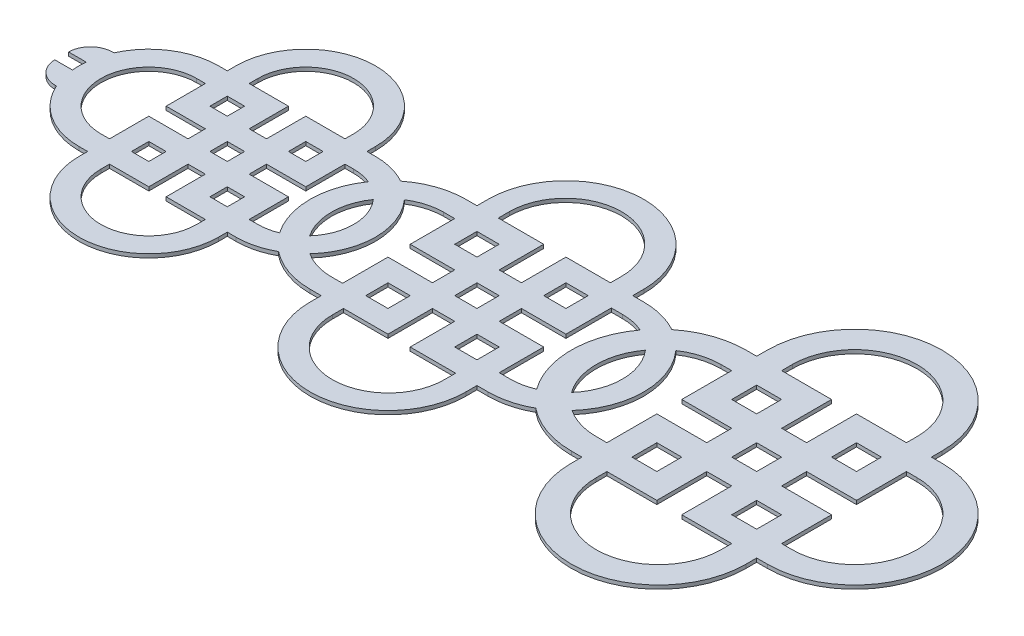
SolidWorks part; units mm, degrees
material "Acrylic (Medium-high impact)"
ref_plane "Front Plane" through (0, 0, 0) normal (0, 0, 1) x (1, 0, 0)
ref_plane "Top Plane" through (0, 0, 0) normal (0, 1, 0) x (1, 0, 0)
ref_plane "Right Plane" through (0, 0, 0) normal (1, 0, 0) x (0, 0, -1)
sketch "스케치1" plane through (0, 0, 0) normal (0, 1, 0) x (1, 0, 0)
  line L0 (0, 10.16) -> (0, -10.16) construction
  line L1 (-50.8, -10.16) -> (50.8, -10.16) construction
  line L2 (-50.8, -10.16) -> (-50.8, 10.16) construction
  line L3 (-50.8, 10.16) -> (50.8, 10.16) construction
  line L4 (50.8, -10.16) -> (50.8, 10.16) construction
  line L5 (-50.8, -10.16) -> (50.8, 10.16) construction
  line L6 (-50.8, 10.16) -> (50.8, -10.16) construction
  line L7 (-35.2629, 0) -> (-46.0171, 0) construction
  line L8 (-45.4229, -4.7829) -> (-35.8571, -4.7829)
  line L9 (-45.4229, -4.7829) -> (-45.4229, 4.7829)
  line L10 (-45.4229, 4.7829) -> (-35.8571, 4.7829)
  line L11 (-35.8571, -4.7829) -> (-35.8571, 4.7829)
  line L12 (-45.4229, -4.7829) -> (-35.8571, 4.7829) construction
  line L13 (-45.4229, 4.7829) -> (-35.8571, -4.7829) construction
  line L14 (-45.4229, 10.16) -> (-35.8571, 10.16)
  line L15 (-45.4229, 10.16) -> (-45.4229, 0.5943)
  line L16 (-45.4229, 0.5943) -> (-35.8571, 0.5943)
  line L17 (-35.8571, 10.16) -> (-35.8571, 0.5943)
  line L18 (-45.4229, 10.16) -> (-35.8571, 0.5943) construction
  line L19 (-45.4229, 0.5943) -> (-35.8571, 10.16) construction
  line L20 (-45.4229, -10.16) -> (-35.8571, -10.16)
  line L21 (-45.4229, -10.16) -> (-45.4229, -0.5943)
  line L22 (-45.4229, -0.5943) -> (-35.8571, -0.5943)
  line L23 (-35.8571, -10.16) -> (-35.8571, -0.5943)
  line L24 (-45.4229, -10.16) -> (-35.8571, -0.5943) construction
  line L25 (-45.4229, -0.5943) -> (-35.8571, -10.16) construction
  line L26 (-30.48, -4.7829) -> (-40.0457, -4.7829)
  line L27 (-30.48, -4.7829) -> (-30.48, 4.7829)
  line L28 (-30.48, 4.7829) -> (-40.0457, 4.7829)
  line L29 (-40.0457, -4.7829) -> (-40.0457, 4.7829)
  line L30 (-30.48, -4.7829) -> (-40.0457, 4.7829) construction
  line L31 (-30.48, 4.7829) -> (-40.0457, -4.7829) construction
  line L32 (-50.8, -4.7829) -> (-41.2343, -4.7829)
  line L33 (-50.8, -4.7829) -> (-50.8, 4.7829)
  line L34 (-50.8, 4.7829) -> (-41.2343, 4.7829)
  line L35 (-41.2343, -4.7829) -> (-41.2343, 4.7829)
  line L36 (-50.8, -4.7829) -> (-41.2343, 4.7829) construction
  line L37 (-50.8, 4.7829) -> (-41.2343, -4.7829) construction
  line L38 (-40.64, 5.3771) -> (-40.64, -5.3771) construction
  line L39 (-49.3, -3.2829) -> (-49.3, 3.2829)
  line L40 (-49.3, 3.2829) -> (-42.7343, 3.2829)
  line L41 (-42.7343, -3.2829) -> (-42.7343, 3.2829)
  line L42 (-49.3, -3.2829) -> (-42.7343, -3.2829)
  line L43 (-43.9229, 8.66) -> (-43.9229, 2.0943)
  line L44 (-43.9229, 2.0943) -> (-37.3571, 2.0943)
  line L45 (-37.3571, 8.66) -> (-37.3571, 2.0943)
  line L46 (-43.9229, 8.66) -> (-37.3571, 8.66)
  line L47 (-40.0457, 0) -> (-41.2343, 0) construction
  line L48 (-38.5457, -3.2829) -> (-31.98, -3.2829)
  line L49 (-38.5457, -3.2829) -> (-38.5457, 3.2829)
  line L50 (-38.5457, 3.2829) -> (-31.98, 3.2829)
  line L51 (-31.98, -3.2829) -> (-31.98, 3.2829)
  line L52 (-38.5457, -3.2829) -> (-31.98, 3.2829) construction
  line L53 (-38.5457, 3.2829) -> (-31.98, -3.2829) construction
  line L58 (-43.9229, 3.1779) -> (-42.7343, 3.1779) construction
  line L60 (-43.9229, -2.0943) -> (-37.3571, -2.0943)
  line L61 (-43.9229, -2.0943) -> (-43.9229, -8.66)
  line L62 (-43.9229, -8.66) -> (-37.3571, -8.66)
  line L63 (-37.3571, -2.0943) -> (-37.3571, -8.66)
  line L64 (-43.9229, -2.0943) -> (-37.3571, -8.66) construction
  line L65 (-43.9229, -8.66) -> (-37.3571, -2.0943) construction
  point P0 (0, 0)
  point P8 (-40.64, 0)
  point P13 (-40.64, 5.3771)
  point P18 (-40.64, -5.3771)
  point P23 (-35.2629, 0)
  point P28 (-46.0171, 0)
  point P39 (-43.7716, 3.1316)
  dimension "D1" = 20.32
  dimension "D2" = 101.6
  dimension "D3" = 1.5
  dimension "D4" = 1.5
  dimension "D5" = 1.5
  dimension "D6" = 1.5
  dimension "D7" = 1.5
  dimension "D8" = 1.5
  dimension "D9" = 1.5
  dimension "D10" = 1.5
  dimension "D11" = 1.5
sketch "스케치2" plane through (0, 0, 0) normal (0, 1, 0) x (1, 0, 0)
  line L0 (-50.8, 4.7829) -> (-41.2343, 4.7829) construction
  line L1 (-50.8, -4.7829) -> (-41.2343, -4.7829) construction
  line L2 (-46.0171, 4.7829) -> (-45.4229, 4.7829)
  line L3 (-35.8571, 5.3771) -> (-35.8571, 4.7829)
  line L5 (-46.0171, -4.7829) -> (-45.4229, -4.7829)
  line L6 (-37.3571, 5.3771) -> (-37.3571, 4.7829)
  line L8 (-43.9229, 4.7829) -> (-43.9229, 5.3771)
  line L10 (-45.4229, 5.3771) -> (-45.4229, 4.7829)
  line L12 (-35.2629, -4.7829) -> (-35.8571, -4.7829)
  line L14 (-35.2629, -3.2829) -> (-35.8571, -3.2829)
  line L16 (-43.9229, 2.0943) -> (-43.9229, 3.2829)
  line L17 (-49.3, 3.2829) -> (-42.7343, 3.2829) construction
  line L18 (-43.9229, 8.66) -> (-43.9229, 2.0943) construction
  line L19 (-43.9229, 3.2829) -> (-42.7343, 3.2829)
  line L20 (-42.7343, 3.2829) -> (-42.7343, 2.0943)
  line L21 (-42.7343, -3.2829) -> (-42.7343, 3.2829) construction
  line L22 (-43.9229, 2.0943) -> (-37.3571, 2.0943) construction
  line L23 (-42.7343, 2.0943) -> (-43.9229, 2.0943)
  line L24 (-41.2343, 0.5943) -> (-41.2343, -0.5943)
  line L25 (-45.4229, 0.5943) -> (-35.8571, 0.5943) construction
  line L26 (-41.2343, -4.7829) -> (-41.2343, 4.7829) construction
  line L27 (-45.4229, -0.5943) -> (-35.8571, -0.5943) construction
  line L28 (-41.2343, -0.5943) -> (-40.0457, -0.5943)
  line L29 (-40.0457, -0.5943) -> (-40.0457, 0.5943)
  line L30 (-40.0457, -4.7829) -> (-40.0457, 4.7829) construction
  line L31 (-40.0457, 0.5943) -> (-41.2343, 0.5943)
  line L32 (-43.9229, -2.0943) -> (-42.7343, -2.0943)
  line L33 (-43.9229, -2.0943) -> (-37.3571, -2.0943) construction
  line L34 (-42.7343, -2.0943) -> (-42.7343, -3.2829)
  line L35 (-42.7343, -3.2829) -> (-43.9229, -3.2829)
  line L36 (-49.3, -3.2829) -> (-42.7343, -3.2829) construction
  line L37 (-43.9229, -3.2829) -> (-43.9229, -2.0943)
  line L38 (-37.3571, -2.0943) -> (-37.3571, -3.2829)
  line L39 (-38.5457, -3.2829) -> (-31.98, -3.2829) construction
  line L40 (-37.3571, -2.0943) -> (-37.3571, -8.66) construction
  line L41 (-37.3571, -3.2829) -> (-38.5457, -3.2829)
  line L42 (-38.5457, -3.2829) -> (-38.5457, -2.0943)
  line L43 (-38.5457, -3.2829) -> (-38.5457, 3.2829) construction
  line L44 (-38.5457, -2.0943) -> (-37.3571, -2.0943)
  line L45 (-37.3571, 2.0943) -> (-37.3571, 3.2829)
  line L46 (-37.3571, 8.66) -> (-37.3571, 2.0943) construction
  line L47 (-38.5457, 3.2829) -> (-31.98, 3.2829) construction
  line L48 (-37.3571, 3.2829) -> (-38.5457, 3.2829)
  line L49 (-38.5457, 3.2829) -> (-38.5457, 2.0943)
  line L50 (-38.5457, 2.0943) -> (-37.3571, 2.0943)
  line L51 (-46.0171, 3.2829) -> (-45.4229, 3.2829)
  line L52 (-45.4229, -4.7829) -> (-45.4229, 4.7829) construction
  line L53 (-45.4229, 3.2829) -> (-45.4229, 0.5943)
  line L54 (-45.4229, 0.5943) -> (-42.7343, 0.5943)
  line L55 (-42.7343, 0.5943) -> (-42.7343, -0.5943)
  line L56 (-42.7343, -0.5943) -> (-45.4229, -0.5943)
  line L57 (-45.4229, -0.5943) -> (-45.4229, -3.2829)
  line L58 (-45.4229, -3.2829) -> (-46.0171, -3.2829)
  line L59 (-41.2343, 4.7829) -> (-41.2343, 2.0943)
  line L60 (-41.2343, 2.0943) -> (-40.0457, 2.0943)
  line L61 (-40.0457, 2.0943) -> (-40.0457, 4.7829)
  line L62 (-40.0457, 4.7829) -> (-37.3571, 4.7829)
  line L63 (-45.4229, 4.7829) -> (-35.8571, 4.7829) construction
  line L64 (-35.8571, 3.2829) -> (-35.8571, 0.5943)
  line L65 (-35.8571, -4.7829) -> (-35.8571, 4.7829) construction
  line L66 (-35.8571, 0.5943) -> (-38.5457, 0.5943)
  line L67 (-38.5457, 0.5943) -> (-38.5457, -0.5943)
  line L68 (-38.5457, -0.5943) -> (-35.8571, -0.5943)
  line L69 (-35.8571, -0.5943) -> (-35.8571, -3.2829)
  line L70 (-35.8571, 3.2829) -> (-35.2629, 3.2829)
  line L71 (-43.9229, -4.7829) -> (-41.2343, -4.7829)
  line L72 (-45.4229, -4.7829) -> (-35.8571, -4.7829) construction
  line L73 (-41.2343, -4.7829) -> (-41.2343, -2.0943)
  line L74 (-41.2343, -2.0943) -> (-40.0457, -2.0943)
  line L75 (-40.0457, -2.0943) -> (-40.0457, -4.7829)
  line L76 (-40.0457, -4.7829) -> (-37.3571, -4.7829)
  line L77 (-35.2629, 4.7829) -> (-35.8571, 4.7829)
  line L78 (-45.4229, -5.3771) -> (-45.4229, -4.7829)
  line L79 (-43.9229, -2.0943) -> (-43.9229, -8.66) construction
  line L80 (-41.2343, 4.7829) -> (-43.9229, 4.7829)
  line L81 (-43.9229, -5.3771) -> (-43.9229, -4.7829)
  line L82 (-50.8, -4.7829) -> (-50.8, 4.7829) construction
  line L83 (-37.3571, -4.7829) -> (-37.3571, -5.3771)
  line L84 (-35.8571, -5.3771) -> (-35.8571, -4.7829)
  arc A0 (-46.0171, 4.7829) -> (-46.0171, -4.7829) centre (-46.0171, 0) ccw
  arc A1 (-46.0171, 3.2829) -> (-46.0171, -3.2829) centre (-46.0171, 0) ccw
  arc A2 (-35.8571, 5.3771) -> (-45.4229, 5.3771) centre (-40.64, 5.3771) ccw
  arc A3 (-37.3571, 5.3771) -> (-43.9229, 5.3771) centre (-40.64, 5.3771) ccw
  arc A4 (-35.2629, -4.7829) -> (-35.2629, 4.7829) centre (-35.2629, 0) ccw
  arc A5 (-35.2629, -3.2829) -> (-35.2629, 3.2829) centre (-35.2629, 0) ccw
  arc A6 (-45.4229, -5.3771) -> (-35.8571, -5.3771) centre (-40.64, -5.3771) ccw
  arc A7 (-43.9229, -5.3771) -> (-37.3571, -5.3771) centre (-40.64, -5.3771) ccw
  point P153 (-40.64, 0)
  dimension "D1" = 4
extrude "보스-돌출1" add sketch "스케치2" along normal blind 0.254
sketch "스케치3" plane through (0, 0.254, 0) normal (0, 1, 0) x (1, 0, 0)
  line L0 (-46.0171, 3.2829) -> (-45.4229, 3.2829) construction
  line L1 (-45.4229, 3.2829) -> (-45.4229, 0.5943) construction
  line L2 (-43.9229, 4.7829) -> (-43.9229, 5.3771) construction
  line L3 (-37.3571, 5.3771) -> (-37.3571, 4.7829) construction
  line L4 (-40.0457, 4.7829) -> (-37.3571, 4.7829) construction
  line L5 (-40.0457, 2.0943) -> (-40.0457, 4.7829) construction
  line L6 (-41.2343, 2.0943) -> (-40.0457, 2.0943) construction
  line L7 (-40.0457, 0.5943) -> (-41.2343, 0.5943) construction
  line L8 (-46.0171, -4.7829) -> (-45.4229, -4.7829)
  line L9 (-45.4229, -4.7829) -> (-45.4229, -5.3771)
  line L10 (-35.8571, -5.3771) -> (-35.8571, -4.7829)
  line L11 (-35.8571, -4.7829) -> (-35.2629, -4.7829)
  line L12 (-35.2629, 4.7829) -> (-35.8571, 4.7829)
  line L13 (-35.8571, 4.7829) -> (-35.8571, 5.3771)
  line L14 (-45.4229, 5.3771) -> (-45.4229, 4.7829)
  line L15 (-45.4229, 4.7829) -> (-46.0171, 4.7829)
  line L16 (-46.0171, -4.7829) -> (-45.4229, -4.7829)
  line L17 (-45.4229, -4.7829) -> (-45.4229, -5.3771)
  line L20 (-35.2629, 4.7829) -> (-35.8571, 4.7829)
  line L21 (-35.8571, 4.7829) -> (-35.8571, 5.3771)
  line L22 (-45.4229, 5.3771) -> (-45.4229, 4.7829)
  line L23 (-45.4229, 4.7829) -> (-46.0171, 4.7829)
  line L24 (-41.2343, 0.5943) -> (-41.2343, -0.5943) construction
  line L25 (-42.7343, 0.5943) -> (-42.7343, -0.5943) construction
  line L26 (-42.7343, -0.5943) -> (-45.4229, -0.5943) construction
  line L27 (-45.4229, -0.5943) -> (-45.4229, -3.2829) construction
  line L28 (-45.4229, -3.2829) -> (-46.0171, -3.2829) construction
  line L29 (-45.4229, 0.5943) -> (-42.7343, 0.5943) construction
  line L30 (-42.7343, 2.0943) -> (-43.9229, 2.0943) construction
  line L31 (-42.7343, 3.2829) -> (-42.7343, 2.0943) construction
  line L32 (-43.9229, 2.0943) -> (-43.9229, 3.2829) construction
  line L33 (-43.9229, 3.2829) -> (-42.7343, 3.2829) construction
  line L34 (-41.2343, 4.7829) -> (-41.2343, 2.0943) construction
  line L35 (-41.2343, 4.7829) -> (-43.9229, 4.7829) construction
  line L36 (-37.3571, 5.3771) -> (-37.3571, 4.7829)
  line L37 (-40.0457, 4.7829) -> (-37.3571, 4.7829)
  line L38 (-40.0457, 2.0943) -> (-40.0457, 4.7829)
  line L39 (-41.2343, 2.0943) -> (-40.0457, 2.0943)
  line L40 (-40.0457, 0.5943) -> (-41.2343, 0.5943)
  line L41 (-41.2343, 0.5943) -> (-41.2343, -0.5943)
  line L42 (-42.7343, 0.5943) -> (-42.7343, -0.5943)
  line L43 (-42.7343, -0.5943) -> (-45.4229, -0.5943)
  line L44 (-45.4229, -0.5943) -> (-45.4229, -3.2829)
  line L45 (-45.4229, -3.2829) -> (-46.0171, -3.2829)
  line L46 (-46.0171, 3.2829) -> (-45.4229, 3.2829)
  line L47 (-45.4229, 3.2829) -> (-45.4229, 0.5943)
  line L48 (-45.4229, 0.5943) -> (-42.7343, 0.5943)
  line L49 (-42.7343, 2.0943) -> (-43.9229, 2.0943)
  line L50 (-42.7343, 3.2829) -> (-42.7343, 2.0943)
  line L51 (-43.9229, 2.0943) -> (-43.9229, 3.2829)
  line L52 (-43.9229, 3.2829) -> (-42.7343, 3.2829)
  line L53 (-41.2343, 4.7829) -> (-41.2343, 2.0943)
  line L54 (-41.2343, 4.7829) -> (-43.9229, 4.7829)
  line L55 (-43.9229, 4.7829) -> (-43.9229, 5.3771)
  line L56 (-40.0457, -0.5943) -> (-40.0457, 0.5943) construction
  line L57 (-41.2343, -0.5943) -> (-40.0457, -0.5943) construction
  line L58 (-38.5457, 3.2829) -> (-38.5457, 2.0943) construction
  line L59 (-38.5457, 2.0943) -> (-37.3571, 2.0943) construction
  line L60 (-37.3571, 2.0943) -> (-37.3571, 3.2829) construction
  line L61 (-37.3571, 3.2829) -> (-38.5457, 3.2829) construction
  line L62 (-42.7343, -2.0943) -> (-42.7343, -3.2829) construction
  line L63 (-43.9229, -2.0943) -> (-42.7343, -2.0943) construction
  line L64 (-43.9229, -3.2829) -> (-43.9229, -2.0943) construction
  line L65 (-42.7343, -3.2829) -> (-43.9229, -3.2829) construction
  line L66 (-42.7343, -2.0943) -> (-42.7343, -3.2829)
  line L67 (-43.9229, -2.0943) -> (-42.7343, -2.0943)
  line L68 (-43.9229, -3.2829) -> (-43.9229, -2.0943)
  line L69 (-42.7343, -3.2829) -> (-43.9229, -3.2829)
  line L70 (-41.2343, -0.5943) -> (-40.0457, -0.5943)
  line L71 (-40.0457, -0.5943) -> (-40.0457, 0.5943)
  line L72 (-37.3571, 2.0943) -> (-37.3571, 3.2829)
  line L73 (-37.3571, 3.2829) -> (-38.5457, 3.2829)
  line L74 (-38.5457, 3.2829) -> (-38.5457, 2.0943)
  line L75 (-38.5457, 2.0943) -> (-37.3571, 2.0943)
  line L76 (-43.9229, -4.7829) -> (-41.2343, -4.7829) construction
  line L77 (-43.9229, -5.3771) -> (-43.9229, -4.7829) construction
  line L78 (-41.2343, -2.0943) -> (-40.0457, -2.0943) construction
  line L79 (-41.2343, -4.7829) -> (-41.2343, -2.0943) construction
  line L80 (-40.0457, -2.0943) -> (-40.0457, -4.7829) construction
  line L81 (-37.3571, -4.7829) -> (-37.3571, -5.3771) construction
  line L82 (-40.0457, -4.7829) -> (-37.3571, -4.7829) construction
  line L83 (-41.2343, -2.0943) -> (-40.0457, -2.0943)
  line L84 (-41.2343, -4.7829) -> (-41.2343, -2.0943)
  line L85 (-40.0457, -2.0943) -> (-40.0457, -4.7829)
  line L86 (-37.3571, -4.7829) -> (-37.3571, -5.3771)
  line L87 (-40.0457, -4.7829) -> (-37.3571, -4.7829)
  line L88 (-43.9229, -5.3771) -> (-43.9229, -4.7829)
  line L89 (-43.9229, -4.7829) -> (-41.2343, -4.7829)
  line L90 (-35.8571, 3.2829) -> (-35.2629, 3.2829) construction
  line L91 (-35.2629, -3.2829) -> (-35.8571, -3.2829) construction
  line L92 (-37.3571, -2.0943) -> (-37.3571, -3.2829) construction
  line L93 (-37.3571, -3.2829) -> (-38.5457, -3.2829) construction
  line L94 (-38.5457, -3.2829) -> (-38.5457, -2.0943) construction
  line L95 (-38.5457, -2.0943) -> (-37.3571, -2.0943) construction
  line L96 (-38.5457, -0.5943) -> (-35.8571, -0.5943) construction
  line L97 (-38.5457, 0.5943) -> (-38.5457, -0.5943) construction
  line L98 (-35.8571, 0.5943) -> (-38.5457, 0.5943) construction
  line L99 (-35.8571, 3.2829) -> (-35.8571, 0.5943) construction
  line L100 (-35.8571, -0.5943) -> (-35.8571, -3.2829) construction
  line L101 (-35.8571, 3.2829) -> (-35.2629, 3.2829)
  line L102 (-35.2629, -3.2829) -> (-35.8571, -3.2829)
  line L103 (-37.3571, -2.0943) -> (-37.3571, -3.2829)
  line L104 (-37.3571, -3.2829) -> (-38.5457, -3.2829)
  line L105 (-38.5457, -3.2829) -> (-38.5457, -2.0943)
  line L106 (-38.5457, -2.0943) -> (-37.3571, -2.0943)
  line L107 (-38.5457, -0.5943) -> (-36.0309, -0.5943)
  line L108 (-38.5457, 0.5943) -> (-38.5457, -0.5943)
  line L109 (-36.0309, 0.5943) -> (-38.5457, 0.5943)
  line L110 (-35.8571, 3.2829) -> (-35.8571, 1.4045)
  line L111 (-35.8571, -1.4045) -> (-35.8571, -3.2829)
  line L112 (-6.3931, 1.4045) -> (-6.3931, 0.5943)
  line L113 (-26.2914, -4.7829) -> (-35.8571, -4.7829) construction
  line L116 (-35.8571, -4.7829) -> (-35.8571, 4.7829) construction
  line L117 (-26.2914, -4.7829) -> (-35.8571, 4.7829) construction
  line L118 (-6.3931, 0.5943) -> (-6.5669, 0.5943)
  line L119 (-31.2851, -4.7829) -> (-30.6909, -4.7829)
  line L120 (-30.6909, -4.7829) -> (-30.6909, -5.3771)
  line L121 (-21.1251, -5.3771) -> (-21.1251, -4.7829)
  line L122 (-21.1251, -4.7829) -> (-20.5309, -4.7829)
  line L123 (-20.5309, 4.7829) -> (-21.1251, 4.7829)
  line L124 (-21.1251, 4.7829) -> (-21.1251, 5.3771)
  line L125 (-30.6909, 5.3771) -> (-30.6909, 4.7829)
  line L126 (-30.6909, 4.7829) -> (-31.2851, 4.7829)
  line L127 (-22.6251, 5.3771) -> (-22.6251, 4.7829)
  line L128 (-25.3137, 4.7829) -> (-22.6251, 4.7829)
  line L129 (-25.3137, 2.0943) -> (-25.3137, 4.7829)
  line L130 (-26.5023, 2.0943) -> (-25.3137, 2.0943)
  line L131 (-25.3137, 0.5943) -> (-26.5023, 0.5943)
  line L132 (-26.5023, 0.5943) -> (-26.5023, -0.5943)
  line L133 (-28.0023, 0.5943) -> (-28.0023, -0.5943)
  line L134 (-28.0023, -0.5943) -> (-30.5171, -0.5943)
  line L135 (-30.6909, -1.4045) -> (-30.6909, -3.2829)
  line L136 (-30.6909, -3.2829) -> (-31.2851, -3.2829)
  line L137 (-31.2851, 3.2829) -> (-30.6909, 3.2829)
  line L138 (-30.6909, 3.2829) -> (-30.6909, 1.4045)
  line L139 (-30.5171, 0.5943) -> (-28.0023, 0.5943)
  line L140 (-28.0023, 2.0943) -> (-29.1909, 2.0943)
  line L141 (-28.0023, 3.2829) -> (-28.0023, 2.0943)
  line L142 (-29.1909, 2.0943) -> (-29.1909, 3.2829)
  line L143 (-29.1909, 3.2829) -> (-28.0023, 3.2829)
  line L144 (-26.5023, 4.7829) -> (-26.5023, 2.0943)
  line L145 (-26.5023, 4.7829) -> (-29.1909, 4.7829)
  line L146 (-29.1909, 4.7829) -> (-29.1909, 5.3771)
  line L147 (-28.0023, -2.0943) -> (-28.0023, -3.2829)
  line L148 (-29.1909, -2.0943) -> (-28.0023, -2.0943)
  line L149 (-29.1909, -3.2829) -> (-29.1909, -2.0943)
  line L150 (-28.0023, -3.2829) -> (-29.1909, -3.2829)
  line L151 (-26.5023, -0.5943) -> (-25.3137, -0.5943)
  line L152 (-25.3137, -0.5943) -> (-25.3137, 0.5943)
  line L153 (-22.6251, 2.0943) -> (-22.6251, 3.2829)
  line L154 (-22.6251, 3.2829) -> (-23.8137, 3.2829)
  line L155 (-23.8137, 3.2829) -> (-23.8137, 2.0943)
  line L156 (-23.8137, 2.0943) -> (-22.6251, 2.0943)
  line L157 (-26.5023, -2.0943) -> (-25.3137, -2.0943)
  line L158 (-26.5023, -4.7829) -> (-26.5023, -2.0943)
  line L159 (-25.3137, -2.0943) -> (-25.3137, -4.7829)
  line L160 (-22.6251, -4.7829) -> (-22.6251, -5.3771)
  line L161 (-25.3137, -4.7829) -> (-22.6251, -4.7829)
  line L162 (-29.1909, -5.3771) -> (-29.1909, -4.7829)
  line L163 (-29.1909, -4.7829) -> (-26.5023, -4.7829)
  line L164 (-21.1251, 3.2829) -> (-20.5309, 3.2829)
  line L165 (-20.5309, -3.2829) -> (-21.1251, -3.2829)
  line L166 (-22.6251, -2.0943) -> (-22.6251, -3.2829)
  line L167 (-22.6251, -3.2829) -> (-23.8137, -3.2829)
  line L168 (-23.8137, -3.2829) -> (-23.8137, -2.0943)
  line L169 (-23.8137, -2.0943) -> (-22.6251, -2.0943)
  line L170 (-23.8137, -0.5943) -> (-21.2989, -0.5943)
  line L171 (-23.8137, 0.5943) -> (-23.8137, -0.5943)
  line L172 (-21.2989, 0.5943) -> (-23.8137, 0.5943)
  line L173 (-21.1251, 3.2829) -> (-21.1251, 1.4045)
  line L174 (-21.1251, -1.4045) -> (-21.1251, -3.2829)
  line L175 (-18.542, 7.7954) -> (-18.542, -9.5869) construction
  line L176 (1.4617, 2.0943) -> (0.2731, 2.0943) construction
  line L177 (1.4617, 3.2829) -> (1.4617, 2.0943) construction
  line L178 (0.2731, 3.2829) -> (1.4617, 3.2829) construction
  line L179 (0.2731, 2.0943) -> (0.2731, 3.2829) construction
  line L180 (6.8389, 4.7829) -> (6.8389, 5.3771) construction
  line L181 (4.1503, 4.7829) -> (6.8389, 4.7829) construction
  line L182 (4.1503, 4.7829) -> (4.1503, 2.0943) construction
  line L183 (4.1503, 2.0943) -> (2.9617, 2.0943) construction
  line L184 (2.9617, 2.0943) -> (2.9617, 4.7829) construction
  line L185 (2.9617, 4.7829) -> (0.2731, 4.7829) construction
  line L186 (0.2731, 5.3771) -> (0.2731, 4.7829) construction
  line L187 (8.1651, 0.5943) -> (5.6503, 0.5943) construction
  line L188 (8.3389, 3.2829) -> (8.3389, 1.4045) construction
  line L189 (8.9331, 3.2829) -> (8.3389, 3.2829) construction
  line L190 (8.3389, -3.2829) -> (8.9331, -3.2829) construction
  line L191 (8.3389, -1.4045) -> (8.3389, -3.2829) construction
  line L192 (5.6503, -0.5943) -> (8.1651, -0.5943) construction
  line L193 (5.6503, 0.5943) -> (5.6503, -0.5943) construction
  line L194 (5.6503, 3.2829) -> (5.6503, 2.0943) construction
  line L195 (6.8389, 3.2829) -> (5.6503, 3.2829) construction
  line L196 (6.8389, 2.0943) -> (6.8389, 3.2829) construction
  line L197 (5.6503, 2.0943) -> (6.8389, 2.0943) construction
  line L198 (6.8389, -2.0943) -> (5.6503, -2.0943) construction
  line L199 (6.8389, -3.2829) -> (6.8389, -2.0943) construction
  line L200 (5.6503, -3.2829) -> (6.8389, -3.2829) construction
  line L201 (5.6503, -2.0943) -> (5.6503, -3.2829) construction
  line L202 (4.1503, 0.5943) -> (4.1503, -0.5943) construction
  line L203 (2.9617, 0.5943) -> (4.1503, 0.5943) construction
  line L204 (2.9617, -0.5943) -> (2.9617, 0.5943) construction
  line L205 (4.1503, -0.5943) -> (2.9617, -0.5943) construction
  line L206 (4.1503, -4.7829) -> (4.1503, -2.0943) construction
  line L207 (6.8389, -4.7829) -> (4.1503, -4.7829) construction
  line L208 (6.8389, -5.3771) -> (6.8389, -4.7829) construction
  line L209 (0.2731, -4.7829) -> (0.2731, -5.3771) construction
  line L210 (2.9617, -4.7829) -> (0.2731, -4.7829) construction
  line L211 (2.9617, -2.0943) -> (2.9617, -4.7829) construction
  line L212 (4.1503, -2.0943) -> (2.9617, -2.0943) construction
  line L213 (1.4617, -2.0943) -> (0.2731, -2.0943) construction
  line L214 (1.4617, -3.2829) -> (1.4617, -2.0943) construction
  line L215 (0.2731, -3.2829) -> (1.4617, -3.2829) construction
  line L216 (0.2731, -2.0943) -> (0.2731, -3.2829) construction
  line L217 (1.4617, -0.5943) -> (-1.0531, -0.5943) construction
  line L218 (1.4617, 0.5943) -> (1.4617, -0.5943) construction
  line L219 (-1.0531, 0.5943) -> (1.4617, 0.5943) construction
  line L220 (-1.2269, 3.2829) -> (-1.2269, 1.4045) construction
  line L221 (-1.2269, 3.2829) -> (-1.8211, 3.2829) construction
  line L222 (-1.2269, -1.4045) -> (-1.2269, -3.2829) construction
  line L223 (-1.8211, -3.2829) -> (-1.2269, -3.2829) construction
  line L224 (-6.3931, -3.2829) -> (-5.7989, -3.2829)
  line L225 (-6.3931, -1.4045) -> (-6.3931, -3.2829)
  line L226 (-9.0817, 3.2829) -> (-9.0817, 2.0943)
  line L227 (-7.8931, 3.2829) -> (-9.0817, 3.2829)
  line L228 (-7.8931, 2.0943) -> (-7.8931, 3.2829)
  line L229 (-9.0817, 2.0943) -> (-7.8931, 2.0943)
  line L230 (-6.3931, 3.2829) -> (-6.3931, 1.4045)
  line L231 (-5.7989, 3.2829) -> (-6.3931, 3.2829)
  line L232 (-9.0817, -0.5943) -> (-6.5669, -0.5943)
  line L233 (-9.0817, 0.5943) -> (-9.0817, -0.5943)
  line L234 (-6.5669, 0.5943) -> (-9.0817, 0.5943)
  line L235 (-7.8931, -2.0943) -> (-9.0817, -2.0943)
  line L236 (-7.8931, -3.2829) -> (-7.8931, -2.0943)
  line L237 (-9.0817, -3.2829) -> (-7.8931, -3.2829)
  line L238 (-9.0817, -2.0943) -> (-9.0817, -3.2829)
  line L239 (-10.5817, -4.7829) -> (-10.5817, -2.0943)
  line L240 (-7.8931, -4.7829) -> (-10.5817, -4.7829)
  line L241 (-7.8931, -5.3771) -> (-7.8931, -4.7829)
  line L242 (-14.4589, -4.7829) -> (-14.4589, -5.3771)
  line L243 (-11.7703, -4.7829) -> (-14.4589, -4.7829)
  line L244 (-11.7703, -2.0943) -> (-11.7703, -4.7829)
  line L245 (-10.5817, -2.0943) -> (-11.7703, -2.0943)
  line L246 (-11.7703, -0.5943) -> (-11.7703, 0.5943)
  line L247 (-10.5817, -0.5943) -> (-11.7703, -0.5943)
  line L248 (-10.5817, 0.5943) -> (-10.5817, -0.5943)
  line L249 (-11.7703, 0.5943) -> (-10.5817, 0.5943)
  line L250 (-13.2703, 2.0943) -> (-14.4589, 2.0943)
  line L251 (-13.2703, 3.2829) -> (-13.2703, 2.0943)
  line L252 (-14.4589, 3.2829) -> (-13.2703, 3.2829)
  line L253 (-14.4589, 2.0943) -> (-14.4589, 3.2829)
  line L254 (-13.2703, -2.0943) -> (-14.4589, -2.0943)
  line L255 (-13.2703, -3.2829) -> (-13.2703, -2.0943)
  line L256 (-14.4589, -3.2829) -> (-13.2703, -3.2829)
  line L257 (-14.4589, -2.0943) -> (-14.4589, -3.2829)
  line L258 (-15.9589, 3.2829) -> (-15.9589, 1.4045)
  line L259 (-15.7851, 0.5943) -> (-13.2703, 0.5943)
  line L260 (-13.2703, 0.5943) -> (-13.2703, -0.5943)
  line L261 (-13.2703, -0.5943) -> (-15.7851, -0.5943)
  line L262 (-15.9589, -1.4045) -> (-15.9589, -3.2829)
  line L263 (-16.5531, -3.2829) -> (-15.9589, -3.2829)
  line L264 (-15.9589, 3.2829) -> (-16.5531, 3.2829)
  line L265 (8.3389, 4.7829) -> (8.9331, 4.7829) construction
  line L266 (8.3389, 5.3771) -> (8.3389, 4.7829) construction
  line L267 (-1.2269, 4.7829) -> (-1.2269, 5.3771) construction
  line L268 (-1.8211, 4.7829) -> (-1.2269, 4.7829) construction
  line L269 (-6.3931, 4.7829) -> (-5.7989, 4.7829)
  line L270 (-6.3931, 5.3771) -> (-6.3931, 4.7829)
  line L271 (-15.9589, 4.7829) -> (-15.9589, 5.3771)
  line L272 (-16.5531, 4.7829) -> (-15.9589, 4.7829)
  line L273 (-15.9589, -4.7829) -> (-16.5531, -4.7829)
  line L274 (-15.9589, -5.3771) -> (-15.9589, -4.7829)
  line L275 (-6.3931, -4.7829) -> (-6.3931, -5.3771)
  line L276 (-5.7989, -4.7829) -> (-6.3931, -4.7829)
  line L277 (-1.2269, -4.7829) -> (-1.8211, -4.7829) construction
  line L278 (-1.2269, -5.3771) -> (-1.2269, -4.7829) construction
  line L279 (8.3389, -4.7829) -> (8.3389, -5.3771) construction
  line L280 (8.9331, -4.7829) -> (8.3389, -4.7829) construction
  line L281 (-7.8931, 4.7829) -> (-7.8931, 5.3771)
  line L282 (-10.5817, 4.7829) -> (-7.8931, 4.7829)
  line L283 (-10.5817, 4.7829) -> (-10.5817, 2.0943)
  line L284 (-10.5817, 2.0943) -> (-11.7703, 2.0943)
  line L285 (-11.7703, 2.0943) -> (-11.7703, 4.7829)
  line L286 (-11.7703, 4.7829) -> (-14.4589, 4.7829)
  line L287 (-14.4589, 5.3771) -> (-14.4589, 4.7829)
  line L288 (10.922, 10.16) -> (10.922, -10.16) construction
  line L289 (-50.8, 10.16) -> (50.8, 10.16) construction
  line L290 (-50.8, -10.16) -> (50.8, -10.16) construction
  line L291 (45.6577, -2.0943) -> (44.4691, -2.0943) construction
  line L292 (45.6577, -3.2829) -> (45.6577, -2.0943) construction
  line L293 (44.4691, -3.2829) -> (45.6577, -3.2829) construction
  line L294 (44.4691, -2.0943) -> (44.4691, -3.2829) construction
  line L295 (48.3463, -4.7829) -> (48.3463, -2.0943) construction
  line L296 (51.0349, -4.7829) -> (48.3463, -4.7829) construction
  line L297 (51.0349, -5.3771) -> (51.0349, -4.7829) construction
  line L298 (44.4691, -4.7829) -> (44.4691, -5.3771) construction
  line L299 (47.1577, -4.7829) -> (44.4691, -4.7829) construction
  line L300 (47.1577, -2.0943) -> (47.1577, -4.7829) construction
  line L301 (48.3463, -2.0943) -> (47.1577, -2.0943) construction
  line L302 (60.3897, -0.5943) -> (57.8749, -0.5943) construction
  line L303 (60.3897, 0.5943) -> (60.3897, -0.5943) construction
  line L304 (57.8749, 0.5943) -> (60.3897, 0.5943) construction
  line L305 (57.7011, -1.4045) -> (57.7011, -3.2829) construction
  line L306 (57.1069, -3.2829) -> (57.7011, -3.2829) construction
  line L307 (57.7011, 3.2829) -> (57.7011, 1.4045) construction
  line L308 (57.7011, 3.2829) -> (57.1069, 3.2829) construction
  line L309 (52.5349, 3.2829) -> (52.5349, 1.4045) construction
  line L310 (53.1291, 3.2829) -> (52.5349, 3.2829) construction
  line L311 (52.5349, -3.2829) -> (53.1291, -3.2829) construction
  line L312 (52.5349, -1.4045) -> (52.5349, -3.2829) construction
  line L313 (51.0349, -2.0943) -> (49.8463, -2.0943) construction
  line L314 (51.0349, -3.2829) -> (51.0349, -2.0943) construction
  line L315 (49.8463, -3.2829) -> (51.0349, -3.2829) construction
  line L316 (49.8463, -2.0943) -> (49.8463, -3.2829) construction
  line L317 (47.1577, -0.5943) -> (47.1577, 0.5943) construction
  line L318 (48.3463, -0.5943) -> (47.1577, -0.5943) construction
  line L319 (48.3463, 0.5943) -> (48.3463, -0.5943) construction
  line L320 (47.1577, 0.5943) -> (48.3463, 0.5943) construction
  line L321 (49.8463, -0.5943) -> (52.3611, -0.5943) construction
  line L322 (49.8463, 0.5943) -> (49.8463, -0.5943) construction
  line L323 (52.3611, 0.5943) -> (49.8463, 0.5943) construction
  line L324 (49.8463, 3.2829) -> (49.8463, 2.0943) construction
  line L325 (51.0349, 3.2829) -> (49.8463, 3.2829) construction
  line L326 (51.0349, 2.0943) -> (51.0349, 3.2829) construction
  line L327 (49.8463, 2.0943) -> (51.0349, 2.0943) construction
  line L328 (51.0349, 4.7829) -> (51.0349, 5.3771) construction
  line L329 (48.3463, 4.7829) -> (51.0349, 4.7829) construction
  line L330 (48.3463, 4.7829) -> (48.3463, 2.0943) construction
  line L331 (48.3463, 2.0943) -> (47.1577, 2.0943) construction
  line L332 (47.1577, 2.0943) -> (47.1577, 4.7829) construction
  line L333 (47.1577, 4.7829) -> (44.4691, 4.7829) construction
  line L334 (44.4691, 5.3771) -> (44.4691, 4.7829) construction
  line L335 (45.6577, 2.0943) -> (44.4691, 2.0943) construction
  line L336 (45.6577, 3.2829) -> (45.6577, 2.0943) construction
  line L337 (44.4691, 3.2829) -> (45.6577, 3.2829) construction
  line L338 (44.4691, 2.0943) -> (44.4691, 3.2829) construction
  line L339 (45.6577, 0.5943) -> (45.6577, -0.5943) construction
  line L340 (43.1429, 0.5943) -> (45.6577, 0.5943) construction
  line L341 (45.6577, -0.5943) -> (43.1429, -0.5943) construction
  line L342 (42.9691, 3.2829) -> (42.3749, 3.2829) construction
  line L343 (42.9691, 3.2829) -> (42.9691, 1.4045) construction
  line L344 (42.3749, -3.2829) -> (42.9691, -3.2829) construction
  line L345 (42.9691, -1.4045) -> (42.9691, -3.2829) construction
  line L346 (67.2669, 4.7829) -> (67.8611, 4.7829) construction
  line L347 (67.2669, 5.3771) -> (67.2669, 4.7829) construction
  line L348 (57.7011, 4.7829) -> (57.7011, 5.3771) construction
  line L349 (57.1069, 4.7829) -> (57.7011, 4.7829) construction
  line L350 (52.5349, 4.7829) -> (53.1291, 4.7829) construction
  line L351 (52.5349, 5.3771) -> (52.5349, 4.7829) construction
  line L352 (42.9691, 4.7829) -> (42.9691, 5.3771) construction
  line L353 (42.3749, 4.7829) -> (42.9691, 4.7829) construction
  line L354 (38.3971, 4.7829) -> (37.8029, 4.7829) construction
  line L355 (37.8029, 4.7829) -> (37.8029, 5.3771) construction
  line L356 (28.2371, 5.3771) -> (28.2371, 4.7829) construction
  line L357 (28.2371, 4.7829) -> (27.6429, 4.7829) construction
  line L358 (23.6651, 4.7829) -> (23.0709, 4.7829) construction
  line L359 (23.0709, 4.7829) -> (23.0709, 5.3771) construction
  line L360 (13.5051, 5.3771) -> (13.5051, 4.7829) construction
  line L361 (13.5051, 4.7829) -> (12.9109, 4.7829) construction
  line L362 (12.9109, -4.7829) -> (13.5051, -4.7829) construction
  line L363 (13.5051, -4.7829) -> (13.5051, -5.3771) construction
  line L364 (23.0709, -5.3771) -> (23.0709, -4.7829) construction
  line L365 (23.0709, -4.7829) -> (23.6651, -4.7829) construction
  line L366 (27.6429, -4.7829) -> (28.2371, -4.7829) construction
  line L367 (28.2371, -4.7829) -> (28.2371, -5.3771) construction
  line L368 (37.8029, -5.3771) -> (37.8029, -4.7829) construction
  line L369 (37.8029, -4.7829) -> (38.3971, -4.7829) construction
  line L370 (42.9691, -4.7829) -> (42.3749, -4.7829) construction
  line L371 (42.9691, -5.3771) -> (42.9691, -4.7829) construction
  line L372 (52.5349, -4.7829) -> (52.5349, -5.3771) construction
  line L373 (53.1291, -4.7829) -> (52.5349, -4.7829) construction
  line L374 (57.7011, -4.7829) -> (57.1069, -4.7829) construction
  line L375 (57.7011, -5.3771) -> (57.7011, -4.7829) construction
  line L376 (67.2669, -4.7829) -> (67.2669, -5.3771) construction
  line L377 (67.8611, -4.7829) -> (67.2669, -4.7829) construction
  line L378 (35.1143, 3.2829) -> (35.1143, 2.0943) construction
  line L379 (36.3029, 3.2829) -> (35.1143, 3.2829) construction
  line L380 (36.3029, 2.0943) -> (36.3029, 3.2829) construction
  line L381 (35.1143, 2.0943) -> (36.3029, 2.0943) construction
  line L382 (29.7371, -3.2829) -> (29.7371, -2.0943) construction
  line L383 (30.9257, -3.2829) -> (29.7371, -3.2829) construction
  line L384 (30.9257, -2.0943) -> (30.9257, -3.2829) construction
  line L385 (29.7371, -2.0943) -> (30.9257, -2.0943) construction
  line L386 (37.8029, 3.2829) -> (38.3971, 3.2829) construction
  line L387 (37.8029, 3.2829) -> (37.8029, 1.4045) construction
  line L388 (38.3971, -3.2829) -> (37.8029, -3.2829) construction
  line L389 (37.8029, -1.4045) -> (37.8029, -3.2829) construction
  line L390 (35.1143, -3.2829) -> (35.1143, -2.0943) construction
  line L391 (36.3029, -3.2829) -> (35.1143, -3.2829) construction
  line L392 (36.3029, -2.0943) -> (36.3029, -3.2829) construction
  line L393 (35.1143, -2.0943) -> (36.3029, -2.0943) construction
  line L394 (37.6291, 0.5943) -> (35.1143, 0.5943) construction
  line L395 (35.1143, -0.5943) -> (37.6291, -0.5943) construction
  line L396 (35.1143, 0.5943) -> (35.1143, -0.5943) construction
  line L397 (32.4257, -0.5943) -> (33.6143, -0.5943) construction
  line L398 (32.4257, 0.5943) -> (32.4257, -0.5943) construction
  line L399 (33.6143, 0.5943) -> (32.4257, 0.5943) construction
  line L400 (33.6143, -0.5943) -> (33.6143, 0.5943) construction
  line L401 (29.7371, -4.7829) -> (32.4257, -4.7829) construction
  line L402 (29.7371, -5.3771) -> (29.7371, -4.7829) construction
  line L403 (36.3029, -4.7829) -> (36.3029, -5.3771) construction
  line L404 (33.6143, -4.7829) -> (36.3029, -4.7829) construction
  line L405 (33.6143, -2.0943) -> (33.6143, -4.7829) construction
  line L406 (32.4257, -2.0943) -> (33.6143, -2.0943) construction
  line L407 (32.4257, -4.7829) -> (32.4257, -2.0943) construction
  line L408 (36.3029, 5.3771) -> (36.3029, 4.7829) construction
  line L409 (33.6143, 4.7829) -> (36.3029, 4.7829) construction
  line L410 (33.6143, 2.0943) -> (33.6143, 4.7829) construction
  line L411 (32.4257, 2.0943) -> (33.6143, 2.0943) construction
  line L412 (32.4257, 4.7829) -> (32.4257, 2.0943) construction
  line L413 (32.4257, 4.7829) -> (29.7371, 4.7829) construction
  line L414 (29.7371, 4.7829) -> (29.7371, 5.3771) construction
  line L415 (29.7371, 3.2829) -> (30.9257, 3.2829) construction
  line L416 (29.7371, 2.0943) -> (29.7371, 3.2829) construction
  line L417 (30.9257, 2.0943) -> (29.7371, 2.0943) construction
  line L418 (30.9257, 3.2829) -> (30.9257, 2.0943) construction
  line L419 (30.9257, -0.5943) -> (28.4109, -0.5943) construction
  line L420 (30.9257, 0.5943) -> (30.9257, -0.5943) construction
  line L421 (28.4109, 0.5943) -> (30.9257, 0.5943) construction
  line L422 (28.2371, -1.4045) -> (28.2371, -3.2829) construction
  line L423 (28.2371, -3.2829) -> (27.6429, -3.2829) construction
  line L424 (27.6429, 3.2829) -> (28.2371, 3.2829) construction
  line L425 (28.2371, 3.2829) -> (28.2371, 1.4045) construction
  line L426 (23.0709, 3.2829) -> (23.6651, 3.2829) construction
  line L427 (23.0709, 3.2829) -> (23.0709, 1.4045) construction
  line L428 (23.6651, -3.2829) -> (23.0709, -3.2829) construction
  line L429 (23.0709, -1.4045) -> (23.0709, -3.2829) construction
  line L430 (15.0051, -4.7829) -> (17.6937, -4.7829) construction
  line L431 (15.0051, -5.3771) -> (15.0051, -4.7829) construction
  line L432 (21.5709, -4.7829) -> (21.5709, -5.3771) construction
  line L433 (18.8823, -4.7829) -> (21.5709, -4.7829) construction
  line L434 (18.8823, -2.0943) -> (18.8823, -4.7829) construction
  line L435 (17.6937, -2.0943) -> (18.8823, -2.0943) construction
  line L436 (17.6937, -4.7829) -> (17.6937, -2.0943) construction
  line L437 (15.0051, -3.2829) -> (15.0051, -2.0943) construction
  line L438 (16.1937, -3.2829) -> (15.0051, -3.2829) construction
  line L439 (16.1937, -2.0943) -> (16.1937, -3.2829) construction
  line L440 (15.0051, -2.0943) -> (16.1937, -2.0943) construction
  line L441 (20.3823, -3.2829) -> (20.3823, -2.0943) construction
  line L442 (21.5709, -3.2829) -> (20.3823, -3.2829) construction
  line L443 (21.5709, -2.0943) -> (21.5709, -3.2829) construction
  line L444 (20.3823, -2.0943) -> (21.5709, -2.0943) construction
  line L445 (18.8823, 0.5943) -> (17.6937, 0.5943) construction
  line L446 (18.8823, -0.5943) -> (18.8823, 0.5943) construction
  line L447 (17.6937, -0.5943) -> (18.8823, -0.5943) construction
  line L448 (17.6937, 0.5943) -> (17.6937, -0.5943) construction
  line L449 (22.8971, 0.5943) -> (20.3823, 0.5943) construction
  line L450 (20.3823, 0.5943) -> (20.3823, -0.5943) construction
  line L451 (20.3823, -0.5943) -> (22.8971, -0.5943) construction
  line L452 (20.3823, 3.2829) -> (20.3823, 2.0943) construction
  line L453 (21.5709, 3.2829) -> (20.3823, 3.2829) construction
  line L454 (21.5709, 2.0943) -> (21.5709, 3.2829) construction
  line L455 (20.3823, 2.0943) -> (21.5709, 2.0943) construction
  line L456 (21.5709, 5.3771) -> (21.5709, 4.7829) construction
  line L457 (18.8823, 4.7829) -> (21.5709, 4.7829) construction
  line L458 (18.8823, 2.0943) -> (18.8823, 4.7829) construction
  line L459 (17.6937, 2.0943) -> (18.8823, 2.0943) construction
  line L460 (17.6937, 4.7829) -> (17.6937, 2.0943) construction
  line L461 (17.6937, 4.7829) -> (15.0051, 4.7829) construction
  line L462 (15.0051, 4.7829) -> (15.0051, 5.3771) construction
  line L463 (15.0051, 3.2829) -> (16.1937, 3.2829) construction
  line L464 (15.0051, 2.0943) -> (15.0051, 3.2829) construction
  line L465 (16.1937, 2.0943) -> (15.0051, 2.0943) construction
  line L466 (16.1937, 3.2829) -> (16.1937, 2.0943) construction
  line L467 (13.5051, 3.2829) -> (13.5051, 1.4045) construction
  line L468 (12.9109, 3.2829) -> (13.5051, 3.2829) construction
  line L469 (13.5051, -3.2829) -> (12.9109, -3.2829) construction
  line L470 (13.5051, -1.4045) -> (13.5051, -3.2829) construction
  line L471 (16.1937, -0.5943) -> (13.6789, -0.5943) construction
  line L472 (16.1937, 0.5943) -> (16.1937, -0.5943) construction
  line L473 (13.6789, 0.5943) -> (16.1937, 0.5943) construction
  line L474 (52.3611, 0.5943) -> (52.5349, 0.5943) construction
  line L475 (52.5349, 0.5943) -> (52.5349, 1.4045) construction
  line L476 (52.3611, -0.5943) -> (52.5349, -0.5943) construction
  line L477 (52.5349, -0.5943) -> (52.5349, -1.4045) construction
  line L478 (-35.8571, -5.3771) -> (-35.8571, -4.7829) construction
  line L479 (-35.8571, -5.3771) -> (-35.8571, -4.7829)
  line L480 (-35.2629, -4.7829) -> (-35.8571, -4.7829)
  line L481 (-6.5669, -0.5943) -> (-6.3931, -0.5943)
  line L482 (-6.3931, -0.5943) -> (-6.3931, -1.4045)
  arc A0 (-46.0171, 3.2829) -> (-46.0171, -3.2829) centre (-46.0171, 0) ccw construction
  arc A1 (-37.3571, 5.3771) -> (-43.9229, 5.3771) centre (-40.64, 5.3771) ccw construction
  arc A2 (-46.0171, 3.2829) -> (-46.0171, -3.2829) centre (-46.0171, 0) ccw
  arc A3 (-37.3571, 5.3771) -> (-43.9229, 5.3771) centre (-40.64, 5.3771) ccw
  arc A4 (-46.0171, 4.7829) -> (-46.0171, -4.7829) centre (-46.0171, 0) ccw
  arc A5 (-45.4229, -5.3771) -> (-35.8571, -5.3771) centre (-40.64, -5.3771) ccw
  arc A6 (-35.2629, -4.7829) -> (-35.2629, 4.7829) centre (-35.2629, 0) ccw
  arc A7 (-35.8571, 5.3771) -> (-45.4229, 5.3771) centre (-40.64, 5.3771) ccw
  arc A8 (-46.0171, 4.7829) -> (-46.0171, -4.7829) centre (-46.0171, 0) ccw
  arc A9 (-45.4229, -5.3771) -> (-35.8571, -5.3771) centre (-40.64, -5.3771) ccw
  arc A10 (-35.2629, -4.7829) -> (-33.274, -4.3497) centre (-35.2629, 0) ccw
  arc A11 (-35.8571, 5.3771) -> (-45.4229, 5.3771) centre (-40.64, 5.3771) ccw
  arc A12 (-43.9229, -5.3771) -> (-37.3571, -5.3771) centre (-40.64, -5.3771) ccw construction
  arc A13 (-43.9229, -5.3771) -> (-37.3571, -5.3771) centre (-40.64, -5.3771) ccw
  arc A14 (-35.2629, -3.2829) -> (-35.2629, 3.2829) centre (-35.2629, 0) ccw construction
  arc A15 (-35.2629, -3.2829) -> (-34.7948, -3.2493) centre (-35.2629, 0) ccw
  arc A16 (-31.2851, 3.2829) -> (-31.7532, 3.2493) centre (-31.2851, 0) ccw
  arc A17 (-22.6251, 5.3771) -> (-29.1909, 5.3771) centre (-25.908, 5.3771) ccw
  arc A18 (-31.2851, 4.7829) -> (-33.274, 4.3497) centre (-31.2851, 0) ccw
  arc A19 (-30.6909, -5.3771) -> (-21.1251, -5.3771) centre (-25.908, -5.3771) ccw
  arc A20 (-21.1251, 5.3771) -> (-30.6909, 5.3771) centre (-25.908, 5.3771) ccw
  arc A21 (-29.1909, -5.3771) -> (-22.6251, -5.3771) centre (-25.908, -5.3771) ccw
  arc A22 (-20.5309, -3.2829) -> (-20.0628, -3.2493) centre (-20.5309, 0) ccw
  arc A23 (-20.5309, -4.7829) -> (-18.542, -4.3497) centre (-20.5309, 0) ccw
  arc A24 (-36.0309, 0.5943) -> (-36.0309, -0.5943) centre (-31.2851, 0) ccw
  arc A25 (-35.8571, -1.4045) -> (-34.7948, -3.2493) centre (-31.2851, 0) ccw
  arc A26 (-33.274, -4.3497) -> (-31.2851, -4.7829) centre (-31.2851, 0) ccw
  arc A27 (-34.7948, 3.2493) -> (-35.8571, 1.4045) centre (-31.2851, 0) ccw
  arc A28 (-33.274, -2.6118) -> (-33.274, 2.6118) centre (-35.2629, 0) ccw
  arc A29 (-31.7532, -3.2493) -> (-30.6909, -1.4045) centre (-35.2629, 0) ccw
  arc A30 (-33.274, 2.6118) -> (-33.274, -2.6118) centre (-31.2851, 0) ccw
  arc A31 (-31.7532, -3.2493) -> (-31.2851, -3.2829) centre (-31.2851, 0) ccw
  arc A32 (-34.7948, 3.2493) -> (-35.2629, 3.2829) centre (-35.2629, 0) ccw
  arc A33 (-33.274, 4.3497) -> (-35.2629, 4.7829) centre (-35.2629, 0) ccw
  arc A34 (-30.6909, 1.4045) -> (-31.7532, 3.2493) centre (-35.2629, 0) ccw
  arc A35 (-30.5171, -0.5943) -> (-30.5171, 0.5943) centre (-35.2629, 0) ccw
  arc A36 (0.2731, 5.3771) -> (6.8389, 5.3771) centre (3.556, 5.3771) cw construction
  arc A37 (8.9331, 3.2829) -> (9.4012, 3.2493) centre (8.9331, 0) cw construction
  arc A38 (6.8389, -5.3771) -> (0.2731, -5.3771) centre (3.556, -5.3771) cw construction
  arc A39 (-1.0531, 0.5943) -> (-1.0531, -0.5943) centre (-5.7989, 0) cw construction
  arc A40 (-2.2892, 3.2493) -> (-1.2269, 1.4045) centre (-5.7989, 0) cw construction
  arc A41 (-2.2892, 3.2493) -> (-1.8211, 3.2829) centre (-1.8211, 0) cw construction
  arc A42 (-1.8211, -3.2829) -> (-2.2892, -3.2493) centre (-1.8211, 0) cw construction
  arc A43 (-1.2269, -1.4045) -> (-2.2892, -3.2493) centre (-5.7989, 0) cw construction
  arc A44 (-3.81, 2.6118) -> (-3.81, -2.6118) centre (-5.7989, 0) cw construction
  arc A45 (-3.81, -2.6118) -> (-3.81, 2.6118) centre (-1.8211, 0) cw construction
  arc A46 (-5.3308, -3.2493) -> (-5.7989, -3.2829) centre (-5.7989, 0) cw
  arc A47 (-5.3308, -3.2493) -> (-6.3931, -1.4045) centre (-1.8211, 0) cw construction
  arc A48 (-5.7989, 3.2829) -> (-5.3308, 3.2493) centre (-5.7989, 0) cw
  arc A49 (-6.3931, 1.4045) -> (-5.3308, 3.2493) centre (-1.8211, 0) cw construction
  arc A50 (-6.5669, -0.5943) -> (-6.5669, 0.5943) centre (-1.8211, 0) cw construction
  arc A51 (-7.8931, -5.3771) -> (-14.4589, -5.3771) centre (-11.176, -5.3771) cw
  arc A52 (-16.5531, -3.2829) -> (-17.0212, -3.2493) centre (-16.5531, 0) cw
  arc A53 (-1.2269, 5.3771) -> (8.3389, 5.3771) centre (3.556, 5.3771) cw construction
  arc A54 (-3.81, 4.3497) -> (-1.8211, 4.7829) centre (-1.8211, 0) cw construction
  arc A55 (-5.7989, 4.7829) -> (-3.81, 4.3497) centre (-5.7989, 0) cw
  arc A56 (-15.9589, 5.3771) -> (-6.3931, 5.3771) centre (-11.176, 5.3771) cw
  arc A57 (-16.5531, -4.7829) -> (-18.542, -4.3497) centre (-16.5531, 0) cw
  arc A58 (-6.3931, -5.3771) -> (-15.9589, -5.3771) centre (-11.176, -5.3771) cw
  arc A59 (-3.81, -4.3497) -> (-5.7989, -4.7829) centre (-5.7989, 0) cw
  arc A60 (-1.8211, -4.7829) -> (-3.81, -4.3497) centre (-1.8211, 0) cw construction
  arc A61 (8.3389, -5.3771) -> (-1.2269, -5.3771) centre (3.556, -5.3771) cw construction
  arc A62 (8.9331, 4.7829) -> (10.922, 4.3497) centre (8.9331, 0) cw construction
  arc A63 (-14.4589, 5.3771) -> (-7.8931, 5.3771) centre (-11.176, 5.3771) cw
  arc A64 (-21.1251, 1.4045) -> (-20.0628, 3.2493) centre (-16.5531, 0) cw
  arc A65 (-21.2989, -0.5943) -> (-21.2989, 0.5943) centre (-16.5531, 0) cw
  arc A66 (-18.542, -2.6118) -> (-18.542, 2.6118) centre (-20.5309, 0) ccw
  arc A67 (-20.0628, -3.2493) -> (-21.1251, -1.4045) centre (-16.5531, 0) cw
  arc A68 (-18.542, -2.6118) -> (-18.542, 2.6118) centre (-16.5531, 0) cw
  arc A69 (-17.0212, -3.2493) -> (-15.9589, -1.4045) centre (-20.5309, 0) ccw
  arc A70 (-15.9589, 1.4045) -> (-17.0212, 3.2493) centre (-20.5309, 0) ccw
  arc A71 (-15.7851, -0.5943) -> (-15.7851, 0.5943) centre (-20.5309, 0) ccw
  arc A72 (-17.0212, 3.2493) -> (-16.5531, 3.2829) centre (-16.5531, 0) cw
  arc A73 (-20.0628, 3.2493) -> (-20.5309, 3.2829) centre (-20.5309, 0) ccw
  arc A74 (-18.542, 4.3497) -> (-16.5531, 4.7829) centre (-16.5531, 0) cw
  arc A75 (-18.542, 4.3497) -> (-20.5309, 4.7829) centre (-20.5309, 0) ccw
  arc A76 (51.0349, -5.3771) -> (44.4691, -5.3771) centre (47.752, -5.3771) cw construction
  arc A77 (57.8749, 0.5943) -> (57.8749, -0.5943) centre (53.1291, 0) cw construction
  arc A78 (57.1069, -3.2829) -> (56.6388, -3.2493) centre (57.1069, 0) cw construction
  arc A79 (57.7011, -1.4045) -> (56.6388, -3.2493) centre (53.1291, 0) cw construction
  arc A80 (56.6388, 3.2493) -> (57.7011, 1.4045) centre (53.1291, 0) cw construction
  arc A81 (56.6388, 3.2493) -> (57.1069, 3.2829) centre (57.1069, 0) cw construction
  arc A82 (55.118, 2.6118) -> (55.118, -2.6118) centre (53.1291, 0) cw construction
  arc A83 (55.118, -2.6118) -> (55.118, 2.6118) centre (57.1069, 0) cw construction
  arc A84 (53.1291, 3.2829) -> (53.5972, 3.2493) centre (53.1291, 0) cw construction
  arc A85 (52.5349, 1.4045) -> (53.5972, 3.2493) centre (57.1069, 0) cw construction
  arc A86 (53.5972, -3.2493) -> (53.1291, -3.2829) centre (53.1291, 0) cw construction
  arc A87 (53.5972, -3.2493) -> (52.5349, -1.4045) centre (57.1069, 0) cw construction
  arc A88 (52.3611, -0.5943) -> (52.3611, 0.5943) centre (57.1069, 0) cw construction
  arc A89 (44.4691, 5.3771) -> (51.0349, 5.3771) centre (47.752, 5.3771) cw construction
  arc A90 (43.1429, -0.5943) -> (43.1429, 0.5943) centre (38.3971, 0) ccw construction
  arc A91 (41.9068, 3.2493) -> (42.3749, 3.2829) centre (42.3749, 0) cw construction
  arc A92 (42.9691, 1.4045) -> (41.9068, 3.2493) centre (38.3971, 0) ccw construction
  arc A93 (41.9068, -3.2493) -> (42.9691, -1.4045) centre (38.3971, 0) ccw construction
  arc A94 (42.3749, -3.2829) -> (41.9068, -3.2493) centre (42.3749, 0) cw construction
  arc A95 (57.7011, 5.3771) -> (67.2669, 5.3771) centre (62.484, 5.3771) cw construction
  arc A96 (55.118, 4.3497) -> (57.1069, 4.7829) centre (57.1069, 0) cw construction
  arc A97 (53.1291, 4.7829) -> (55.118, 4.3497) centre (53.1291, 0) cw construction
  arc A98 (42.9691, 5.3771) -> (52.5349, 5.3771) centre (47.752, 5.3771) cw construction
  arc A99 (40.386, 4.3497) -> (42.3749, 4.7829) centre (42.3749, 0) cw construction
  arc A100 (40.386, 4.3497) -> (38.3971, 4.7829) centre (38.3971, 0) ccw construction
  arc A101 (37.8029, 5.3771) -> (28.2371, 5.3771) centre (33.02, 5.3771) ccw construction
  arc A102 (27.6429, 4.7829) -> (25.654, 4.3497) centre (27.6429, 0) ccw construction
  arc A103 (25.654, 4.3497) -> (23.6651, 4.7829) centre (23.6651, 0) ccw construction
  arc A104 (23.0709, 5.3771) -> (13.5051, 5.3771) centre (18.288, 5.3771) ccw construction
  arc A105 (12.9109, 4.7829) -> (10.922, 4.3497) centre (12.9109, 0) ccw construction
  arc A106 (13.5051, -5.3771) -> (23.0709, -5.3771) centre (18.288, -5.3771) ccw construction
  arc A107 (23.6651, -4.7829) -> (25.654, -4.3497) centre (23.6651, 0) ccw construction
  arc A108 (25.654, -4.3497) -> (27.6429, -4.7829) centre (27.6429, 0) ccw construction
  arc A109 (28.2371, -5.3771) -> (37.8029, -5.3771) centre (33.02, -5.3771) ccw construction
  arc A110 (38.3971, -4.7829) -> (40.386, -4.3497) centre (38.3971, 0) ccw construction
  arc A111 (42.3749, -4.7829) -> (40.386, -4.3497) centre (42.3749, 0) cw construction
  arc A112 (52.5349, -5.3771) -> (42.9691, -5.3771) centre (47.752, -5.3771) cw construction
  arc A113 (55.118, -4.3497) -> (53.1291, -4.7829) centre (53.1291, 0) cw construction
  arc A114 (57.1069, -4.7829) -> (55.118, -4.3497) centre (57.1069, 0) cw construction
  arc A115 (67.2669, -5.3771) -> (57.7011, -5.3771) centre (62.484, -5.3771) cw construction
  arc A116 (67.8611, 4.7829) -> (67.8611, -4.7829) centre (67.8611, 0) cw construction
  arc A117 (40.386, -2.6118) -> (40.386, 2.6118) centre (38.3971, 0) ccw construction
  arc A118 (40.386, -2.6118) -> (40.386, 2.6118) centre (42.3749, 0) cw construction
  arc A119 (38.8652, 3.2493) -> (38.3971, 3.2829) centre (38.3971, 0) ccw construction
  arc A120 (37.8029, 1.4045) -> (38.8652, 3.2493) centre (42.3749, 0) cw construction
  arc A121 (38.8652, -3.2493) -> (37.8029, -1.4045) centre (42.3749, 0) cw construction
  arc A122 (38.3971, -3.2829) -> (38.8652, -3.2493) centre (38.3971, 0) ccw construction
  arc A123 (37.6291, -0.5943) -> (37.6291, 0.5943) centre (42.3749, 0) cw construction
  arc A124 (29.7371, -5.3771) -> (36.3029, -5.3771) centre (33.02, -5.3771) ccw construction
  arc A125 (36.3029, 5.3771) -> (29.7371, 5.3771) centre (33.02, 5.3771) ccw construction
  arc A126 (28.4109, -0.5943) -> (28.4109, 0.5943) centre (23.6651, 0) ccw construction
  arc A127 (27.1748, -3.2493) -> (28.2371, -1.4045) centre (23.6651, 0) ccw construction
  arc A128 (27.1748, -3.2493) -> (27.6429, -3.2829) centre (27.6429, 0) ccw construction
  arc A129 (28.2371, 1.4045) -> (27.1748, 3.2493) centre (23.6651, 0) ccw construction
  arc A130 (27.6429, 3.2829) -> (27.1748, 3.2493) centre (27.6429, 0) ccw construction
  arc A131 (25.654, -2.6118) -> (25.654, 2.6118) centre (23.6651, 0) ccw construction
  arc A132 (25.654, 2.6118) -> (25.654, -2.6118) centre (27.6429, 0) ccw construction
  arc A133 (24.1332, 3.2493) -> (23.6651, 3.2829) centre (23.6651, 0) ccw construction
  arc A134 (24.1332, 3.2493) -> (23.0709, 1.4045) centre (27.6429, 0) ccw construction
  arc A135 (23.0709, -1.4045) -> (24.1332, -3.2493) centre (27.6429, 0) ccw construction
  arc A136 (23.6651, -3.2829) -> (24.1332, -3.2493) centre (23.6651, 0) ccw construction
  arc A137 (15.0051, -5.3771) -> (21.5709, -5.3771) centre (18.288, -5.3771) ccw construction
  arc A138 (22.8971, 0.5943) -> (22.8971, -0.5943) centre (27.6429, 0) ccw construction
  arc A139 (21.5709, 5.3771) -> (15.0051, 5.3771) centre (18.288, 5.3771) ccw construction
  arc A140 (12.9109, 3.2829) -> (12.4428, 3.2493) centre (12.9109, 0) ccw construction
  arc A141 (53.5972, 3.2493) -> (55.118, 2.6118) centre (53.1291, 0) cw construction
  arc A142 (55.118, -2.6118) -> (53.5972, -3.2493) centre (53.1291, 0) cw construction
  arc A143 (55.118, 4.3497) -> (55.118, -4.3497) centre (53.1291, 0) cw construction
  arc A144 (8.3389, -1.4045) -> (9.4012, -3.2493) centre (12.9109, 0) ccw construction
  arc A145 (8.1651, 0.5943) -> (8.1651, -0.5943) centre (12.9109, 0) ccw construction
  arc A146 (10.922, 2.6118) -> (10.922, -2.6118) centre (8.9331, 0) cw construction
  arc A147 (9.4012, 3.2493) -> (8.3389, 1.4045) centre (12.9109, 0) ccw construction
  arc A148 (10.922, 2.6118) -> (10.922, -2.6118) centre (12.9109, 0) ccw construction
  arc A149 (12.4428, 3.2493) -> (13.5051, 1.4045) centre (8.9331, 0) cw construction
  arc A150 (13.6789, 0.5943) -> (13.6789, -0.5943) centre (8.9331, 0) cw construction
  arc A151 (13.5051, -1.4045) -> (12.4428, -3.2493) centre (8.9331, 0) cw construction
  arc A152 (12.4428, -3.2493) -> (12.9109, -3.2829) centre (12.9109, 0) ccw construction
  arc A153 (10.922, -4.3497) -> (12.9109, -4.7829) centre (12.9109, 0) ccw construction
  arc A154 (10.922, -4.3497) -> (8.9331, -4.7829) centre (8.9331, 0) cw construction
  arc A155 (9.4012, -3.2493) -> (8.9331, -3.2829) centre (8.9331, 0) cw construction
  arc A156 (-5.3308, 3.2493) -> (-5.3308, -3.2493) centre (-5.7989, 0) cw
  arc A157 (-3.81, 4.3497) -> (-3.81, -4.3497) centre (-5.7989, 0) cw
  point P68 (-31.0743, 0)
  point P74 (-50.8, 0)
  point P145 (-16.3423, 0)
  point P146 (-36.068, 0)
  dimension "D2" = 2
  dimension "D3" = 2.5831
  dimension "D4" = 2.5831
  dimension "D5" = 2.5831
  dimension "D1" = 0
extrude "보스-돌출2" [suppressed] add sketch "스케치3" along normal blind 0.254
sketch "스케치5" plane through (0, 0.254, 0) normal (0, 1, 0) x (1, 0, 0)
  line L0 (-29.6317, 3.81) -> (-29.6317, -3.871) construction
  line L1 (-28.8697, -5.334) -> (-18.2017, -5.334) construction
  line L2 (-28.8697, -5.334) -> (-28.8697, 5.334) construction
  line L3 (-28.8697, 5.334) -> (-18.2017, 5.334) construction
  line L4 (-18.2017, -5.334) -> (-18.2017, 5.334) construction
  line L5 (-28.8697, -5.334) -> (-18.2017, 5.334) construction
  line L6 (-28.8697, 5.334) -> (-18.2017, -5.334) construction
  line L7 (-24.2977, -0.762) -> (-22.7737, -0.762)
  line L8 (-24.2977, -0.762) -> (-24.2977, 0.762)
  line L9 (-24.2977, 0.762) -> (-22.7737, 0.762)
  line L10 (-22.7737, -0.762) -> (-22.7737, 0.762)
  line L11 (-24.2977, -0.762) -> (-22.7737, 0.762) construction
  line L12 (-24.2977, 0.762) -> (-22.7737, -0.762) construction
  line L13 (-27.3457, 2.286) -> (-25.8217, 2.286)
  line L14 (-27.3457, 2.286) -> (-27.3457, 3.81)
  line L15 (-27.3457, 3.81) -> (-25.8217, 3.81)
  line L16 (-25.8217, 2.286) -> (-25.8217, 3.81)
  line L17 (-27.3457, 2.286) -> (-25.8217, 3.81) construction
  line L18 (-27.3457, 3.81) -> (-25.8217, 2.286) construction
  line L19 (-28.8697, 3.81) -> (-28.8697, 5.334)
  line L20 (-25.8217, 3.81) -> (-25.8217, 5.334) construction
  line L21 (-25.8217, 2.286) -> (-25.8217, 0.762) construction
  line L22 (-25.8217, 0.762) -> (-24.2977, 0.762) construction
  line L23 (-27.3457, 2.286) -> (-28.8697, 2.286) construction
  line L24 (-28.8697, 3.81) -> (-28.8697, 0.762)
  line L25 (-28.8697, 0.762) -> (-25.8217, 0.762)
  line L26 (-25.8217, 0.762) -> (-25.8217, -0.762)
  line L27 (-25.8217, -0.762) -> (-28.8697, -0.762)
  line L28 (-28.8697, -0.762) -> (-28.8697, -3.871)
  line L29 (-19.7257, 5.334) -> (-22.7737, 5.334)
  line L30 (-23.5357, 0) -> (-40.0457, 0) construction
  line L31 (-40.0457, -0.5943) -> (-40.0457, 0.5943) construction
  line L32 (-28.8697, 5.334) -> (-28.8697, 6.096)
  line L33 (-28.8697, 6.096) -> (-18.2017, 6.096) construction
  line L34 (-18.2017, 6.096) -> (-18.2017, 5.334)
  line L35 (-18.2017, -6.096) -> (-18.2017, -5.334)
  line L36 (-28.8697, -5.334) -> (-28.8697, -6.096)
  line L37 (-28.8697, 5.334) -> (-29.6317, 5.334)
  line L38 (-29.6317, 5.334) -> (-29.6317, -5.334) construction
  line L39 (-29.6317, -5.334) -> (-28.8697, -5.334)
  line L40 (-23.5357, 0) -> (-23.5357, 5.334) construction
  line L41 (-17.4397, -5.334) -> (-18.2017, -5.334)
  line L42 (-18.2017, 5.334) -> (-17.4397, 5.334)
  line L43 (-21.2497, 3.81) -> (-19.7257, 3.81)
  line L44 (-21.2497, 3.81) -> (-21.2497, 2.286)
  line L45 (-21.2497, 2.286) -> (-19.7257, 2.286)
  line L46 (-19.7257, 3.81) -> (-19.7257, 2.286)
  line L47 (-19.7257, -2.286) -> (-19.7257, -3.81)
  line L48 (-19.7257, -2.286) -> (-21.2497, -2.286)
  line L49 (-21.2497, -2.286) -> (-21.2497, -3.81)
  line L50 (-19.7257, -3.81) -> (-21.2497, -3.81)
  line L51 (-25.8217, -3.81) -> (-27.3457, -3.81)
  line L52 (-25.8217, -3.81) -> (-25.8217, -2.286)
  line L53 (-25.8217, -2.286) -> (-27.3457, -2.286)
  line L54 (-27.3457, -3.81) -> (-27.3457, -2.286)
  line L55 (-28.8697, 3.81) -> (-29.6317, 3.81)
  line L56 (-28.8697, -3.871) -> (-29.6317, -3.871)
  line L57 (-22.7737, 5.334) -> (-22.7737, 2.286)
  line L58 (-22.7737, 2.286) -> (-24.2977, 2.286)
  line L59 (-24.2977, 2.286) -> (-24.2977, 5.334)
  line L60 (-24.2977, 5.334) -> (-27.4067, 5.334)
  line L61 (-27.4067, 5.334) -> (-27.4067, 6.096)
  line L62 (-19.7257, 5.334) -> (-19.7257, 6.096)
  line L63 (-18.2017, -3.81) -> (-18.2017, -0.762)
  line L64 (-18.2017, -0.762) -> (-21.2497, -0.762)
  line L65 (-21.2497, -0.762) -> (-21.2497, 0.762)
  line L66 (-21.2497, 0.762) -> (-18.2017, 0.762)
  line L67 (-18.2017, 0.762) -> (-18.2017, 3.871)
  line L68 (-18.2017, 3.871) -> (-17.4397, 3.871)
  line L69 (-18.2017, -3.81) -> (-17.4397, -3.81)
  line L70 (-27.3457, -5.334) -> (-24.2977, -5.334)
  line L71 (-24.2977, -5.334) -> (-24.2977, -2.286)
  line L72 (-24.2977, -2.286) -> (-22.7737, -2.286)
  line L73 (-22.7737, -2.286) -> (-22.7737, -5.334)
  line L74 (-22.7737, -5.334) -> (-19.6647, -5.334)
  line L75 (-19.6647, -5.334) -> (-19.6647, -6.096)
  line L76 (-27.3457, -5.334) -> (-27.3457, -6.096)
  arc A0 (-28.8697, 6.096) -> (-18.2017, 6.096) centre (-23.5357, 6.096) cw
  arc A1 (-28.8697, -6.096) -> (-18.2017, -6.096) centre (-23.5357, -6.096) ccw
  arc A2 (-29.6317, 5.334) -> (-29.6317, -5.334) centre (-29.6317, 0) ccw
  arc A3 (-17.4397, 5.334) -> (-17.4397, -5.334) centre (-17.4397, 0) cw
  arc A4 (-29.6317, 3.81) -> (-29.6317, -3.871) centre (-29.6317, -0.0305) ccw
  arc A5 (-19.7257, 6.096) -> (-27.4067, 6.096) centre (-23.5662, 6.096) ccw
  arc A6 (-17.4397, -3.81) -> (-17.4397, 3.871) centre (-17.4397, 0.0305) ccw
  arc A7 (-27.3457, -6.096) -> (-19.6647, -6.096) centre (-23.5052, -6.096) ccw
  point P0 (-23.5357, 0)
  point P5 (-23.5357, 0)
  point P10 (-26.5837, 3.048)
  point P28 (-23.5357, 11.43)
  point P29 (-23.5357, -11.43)
  point P52 (-23.5357, 0)
  point P59 (-31.7907, 0)
  point P88 (-23.5357, 0)
  point P93 (-34.9657, 0)
  dimension "D1" = 22.86
  dimension "D2" = 1.524
  dimension "D4" = 4
  dimension "D3" = 4
  dimension "D5" = 3.175
extrude "보스-돌출4" add sketch "스케치5" against normal up to surface (0.254 mm away) contours A4 L55 L37 A2 L39 L36 A1 L35 L41 A3 L42 L34 A0 L32 L24 L25 L26 L27 L28 L56 A7 L76 L70 L71 L72 L73 L74 L75 A6 L69 L63 L64 L65 L66 L67 L68 A5 L62 L29 L57 L58 L59 L60 L61 L16 region at (-28.5464, 0.254, -5.715) up to face at (-45.3096, 0, 0)
sketch "스케치6" plane through (0, 0.254, 0) normal (0, 1, 0) x (1, 0, 0)
  line L0 (-10.3595, 5.9849) -> (-10.3595, 6.7151)
  line L1 (-10.3595, -5.9849) -> (1.6103, -5.9849) construction
  line L2 (-10.3595, -5.9849) -> (-10.3595, 5.9849) construction
  line L3 (-10.3595, 5.9849) -> (1.6103, 5.9849) construction
  line L4 (1.6103, -5.9849) -> (1.6103, 5.9849) construction
  line L5 (-10.3595, -5.9849) -> (1.6103, 5.9849) construction
  line L6 (-10.3595, 5.9849) -> (1.6103, -5.9849) construction
  line L7 (-10.3595, 6.7151) -> (1.6103, 6.7151) construction
  line L8 (1.6103, 6.7151) -> (1.6103, 5.9849)
  line L9 (0, 0) -> (-10.3595, 0) construction
  line L10 (1.6103, -6.7151) -> (1.6103, -5.9849)
  line L11 (-10.3595, -5.9849) -> (-10.3595, -6.7151)
  line L12 (-8.6495, 2.5649) -> (-10.3595, 2.5649) construction
  line L13 (-5.2296, -0.855) -> (-3.5196, -0.855)
  line L14 (-5.2296, -0.855) -> (-5.2296, 0.855)
  line L15 (-5.2296, 0.855) -> (-3.5196, 0.855)
  line L16 (-3.5196, -0.855) -> (-3.5196, 0.855)
  line L17 (-5.2296, -0.855) -> (-3.5196, 0.855) construction
  line L18 (-5.2296, 0.855) -> (-3.5196, -0.855) construction
  line L19 (-8.6495, 2.5649) -> (-6.9395, 2.5649)
  line L20 (-8.6495, 2.5649) -> (-8.6495, 4.2749)
  line L21 (-8.6495, 4.2749) -> (-6.9395, 4.2749)
  line L22 (-6.9395, 2.5649) -> (-6.9395, 4.2749)
  line L23 (-8.6495, 2.5649) -> (-6.9395, 4.2749) construction
  line L24 (-8.6495, 4.2749) -> (-6.9395, 2.5649) construction
  line L25 (-6.9395, 4.2749) -> (-6.9395, 5.9849) construction
  line L26 (-6.9395, 2.5649) -> (-6.9395, 0.855) construction
  line L27 (-6.9395, 0.855) -> (-5.2296, 0.855) construction
  line L28 (-10.3595, 5.9849) -> (-11.0897, 5.9849)
  line L29 (-11.0897, -5.9849) -> (-10.3595, -5.9849)
  line L30 (2.3405, -5.9849) -> (1.6103, -5.9849)
  line L31 (1.6103, 5.9849) -> (2.3405, 5.9849)
  line L32 (-4.3746, 0) -> (-4.3746, -6.7151) construction
  line L33 (-10.3595, 4.2749) -> (-11.0897, 4.2749)
  line L34 (-11.0897, 4.2749) -> (-11.0897, -4.2749) construction
  line L35 (-11.0897, -4.2749) -> (-10.3595, -4.2749)
  line L36 (-11.0897, 5.9849) -> (-11.0897, 4.2749) construction
  line L37 (-10.3595, 4.2749) -> (-10.3595, 0.855)
  line L38 (-10.3595, 0.855) -> (-6.9395, 0.855)
  line L39 (-6.9395, 0.855) -> (-6.9395, -0.855)
  line L40 (-6.9395, -0.855) -> (-10.3595, -0.855)
  line L41 (-10.3595, -0.855) -> (-10.3595, -4.2749)
  line L42 (-1.8096, 4.2749) -> (-0.0997, 4.2749)
  line L43 (-1.8096, 4.2749) -> (-1.8096, 2.5649)
  line L44 (-1.8096, 2.5649) -> (-0.0997, 2.5649)
  line L45 (-0.0997, 4.2749) -> (-0.0997, 2.5649)
  line L46 (-0.0997, -2.5649) -> (-0.0997, -4.2749)
  line L47 (-0.0997, -2.5649) -> (-1.8096, -2.5649)
  line L48 (-1.8096, -2.5649) -> (-1.8096, -4.2749)
  line L49 (-0.0997, -4.2749) -> (-1.8096, -4.2749)
  line L50 (-6.9395, -4.2749) -> (-8.6495, -4.2749)
  line L51 (-6.9395, -4.2749) -> (-6.9395, -2.5649)
  line L52 (-6.9395, -2.5649) -> (-8.6495, -2.5649)
  line L53 (-8.6495, -4.2749) -> (-8.6495, -2.5649)
  line L54 (-4.3746, 0) -> (-6.9395, 2.5649) construction
  line L55 (-5.2296, 5.9849) -> (-8.6495, 5.9849)
  line L56 (-8.6495, 6.7151) -> (-8.6495, 5.9849)
  line L57 (-0.0997, 5.9849) -> (-0.0997, 6.7151)
  line L58 (-0.0997, 5.9849) -> (-3.5196, 5.9849)
  line L59 (-3.5196, 5.9849) -> (-3.5196, 2.5649)
  line L60 (-3.5196, 2.5649) -> (-5.2296, 2.5649)
  line L61 (-5.2296, 2.5649) -> (-5.2296, 5.9849)
  line L62 (1.6103, 0.855) -> (1.6103, 4.2749)
  line L63 (2.3405, 4.2749) -> (1.6103, 4.2749)
  line L64 (1.6103, -4.2749) -> (2.3405, -4.2749)
  line L65 (1.6103, -4.2749) -> (1.6103, -0.855)
  line L66 (1.6103, -0.855) -> (-1.8096, -0.855)
  line L67 (-1.8096, -0.855) -> (-1.8096, 0.855)
  line L68 (-1.8096, 0.855) -> (1.6103, 0.855)
  line L69 (-3.5196, -5.9849) -> (-0.0997, -5.9849)
  line L70 (-0.0997, -6.7151) -> (-0.0997, -5.9849)
  line L71 (-8.6495, -5.9849) -> (-8.6495, -6.7151)
  line L72 (-8.6495, -5.9849) -> (-5.2296, -5.9849)
  line L73 (-5.2296, -5.9849) -> (-5.2296, -2.5649)
  line L74 (-5.2296, -2.5649) -> (-3.5196, -2.5649)
  line L75 (-3.5196, -2.5649) -> (-3.5196, -5.9849)
  line L76 (-6.9395, -0.855) -> (-6.9395, -2.5649) construction
  line L79 (-1.8096, 0.855) -> (-3.5196, 0.855) construction
  arc A0 (-10.3595, 6.7151) -> (1.6103, 6.7151) centre (-4.3746, 6.7151) cw
  arc A1 (-10.3595, -6.7151) -> (1.6103, -6.7151) centre (-4.3746, -6.7151) ccw
  arc A2 (-11.0897, 5.9849) -> (-11.0897, -5.9849) centre (-11.0897, 0) ccw
  arc A3 (2.3405, 5.9849) -> (2.3405, -5.9849) centre (2.3405, 0) cw
  arc A4 (-11.0897, 4.2749) -> (-11.0897, -4.2749) centre (-11.0897, 0) ccw
  arc A5 (-0.0997, 6.7151) -> (-8.6495, 6.7151) centre (-4.3746, 6.7151) ccw
  arc A6 (2.3405, -4.2749) -> (2.3405, 4.2749) centre (2.3405, 0) ccw
  arc A7 (-8.6495, -6.7151) -> (-0.0997, -6.7151) centre (-4.3746, -6.7151) ccw
  point P0 (-4.3746, 0)
  point P8 (-4.3746, 12.7)
  point P15 (-4.3746, -12.7)
  point P16 (-4.3746, 0)
  point P22 (-7.7945, 3.4199)
  dimension "D1" = 25.4
  dimension "D4" = 4
  dimension "D2" = 2
  dimension "D3" = 6.7151
  dimension "D5" = 3.6274
  dimension "D8" = 6.35
  dimension "D6" = 4
extrude "보스-돌출5" add sketch "스케치6" against normal up to surface (0.254 mm away) up to face at (-32.7261, 0, 0.0137)
sketch "스케치7" plane through (0, 0.254, 0) normal (0, 1, 0) x (1, 0, 0)
  line L0 (-51.9834, 0.47) -> (-51.9834, 1.97)
  line L1 (-51.9834, -0.47) -> (-49.6166, -0.47) construction
  line L2 (-51.9834, -0.47) -> (-51.9834, 0.47) construction
  line L3 (-51.9834, 0.47) -> (-49.6166, 0.47) construction
  line L4 (-49.6166, -0.47) -> (-49.6166, 0.47) construction
  line L5 (-51.9834, -0.47) -> (-49.6166, 0.47) construction
  line L6 (-51.9834, 0.47) -> (-49.6166, -0.47) construction
  line L7 (-51.9834, 1.97) -> (-50.3754, 1.97)
  line L8 (-50.7769, 0.47) -> (-51.9834, 0.47)
  line L9 (-50.8, 0) -> (-49.3, 0) construction
  line L10 (-51.9834, -1.97) -> (-50.3754, -1.97)
  line L11 (-51.9834, -0.47) -> (-51.9834, -1.97)
  line L12 (-50.7769, -0.47) -> (-51.9834, -0.47)
  arc A0 (-46.0171, 4.7829) -> (-46.0171, -4.7829) centre (-46.0171, 0) ccw construction
  arc A1 (-50.3754, 1.97) -> (-50.7769, 0.47) centre (-46.0171, 0) ccw
  arc A2 (-46.0171, 3.2829) -> (-46.0171, -3.2829) centre (-46.0171, 0) ccw construction
  arc A3 (-50.3754, -1.97) -> (-50.7769, -0.47) centre (-46.0171, 0) cw
  point P0 (-50.8, 0)
  dimension "D1" = 0.94
  dimension "D2" = 1.2065
  dimension "D3" = 1.5
extrude "보스-돌출6" add sketch "스케치7" against normal up to surface (0.254 mm away) up to face at (-18.3152, 0, -0.0177)
fillet "필렛1" radius 1.524 2 edges at (-51.9834, 0.127, 1.97) (-51.9834, 0.127, -1.97)
